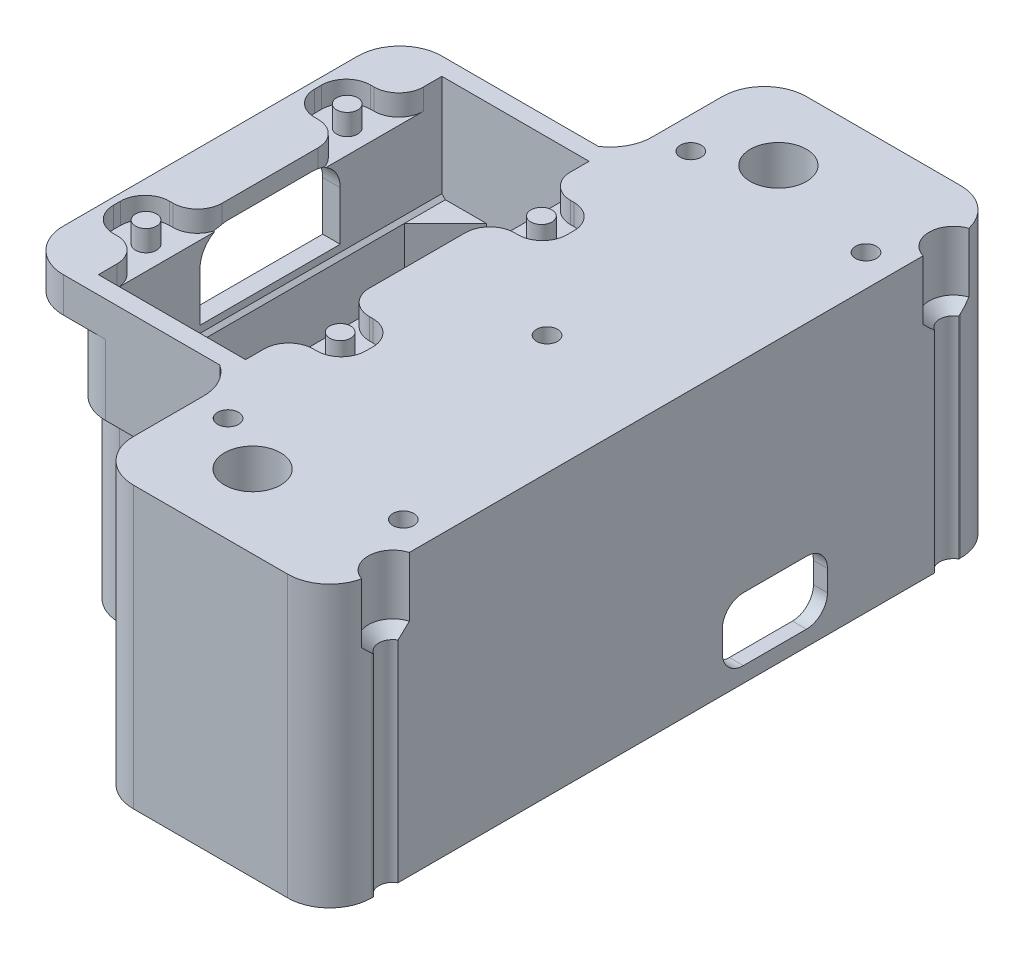
SolidWorks part; units mm, degrees
ref_plane "Płaszczyzna przednia" through (0, 0, 0) normal (0, 0, 1) x (1, 0, 0)
ref_plane "Płaszczyzna górna" through (0, 0, 0) normal (0, 1, 0) x (1, 0, 0)
ref_plane "Płaszczyzna prawa" through (0, 0, 0) normal (1, 0, 0) x (0, 0, -1)
sketch "Szkic1" plane through (0, 0, 0) normal (0, 1, 0) x (1, 0, 0)
  line L0 (0, 14.5) -> (0, -14.5) construction
  line L1 (10, 14.5) -> (10, -14.5)
  line L2 (-10, 14.5) -> (-10, -14.5)
  line L4 (-12, 26) -> (12, 26)
  line L5 (-12, 26) -> (-12, -26)
  line L6 (-12, -26) -> (12, -26)
  line L7 (12, 26) -> (12, -26)
  line L8 (-12, 26) -> (12, -26) construction
  line L9 (-12, -26) -> (12, 26) construction
  arc A0 (10, 14.5) -> (-10, 14.5) centre (0, 14.5) ccw
  arc A1 (-10, -14.5) -> (10, -14.5) centre (0, -14.5) ccw
  point P2 (0, 0)
  point P8 (0, 0)
  dimension "D2" = 10
  dimension "D1" = 29
  dimension "D3" = 24
  dimension "D4" = 52
extrude "Dodanie-wyciągnięcie1" add sketch "Szkic1" along normal blind 25
sketch "Szkic2" plane through (0, 25, 0) normal (0, 1, 0) x (1, 0, 0)
  line L1 (-10.5, 24.5) -> (10.5, 24.5)
  line L2 (-10.5, 24.5) -> (-10.5, -24.5)
  line L3 (-10.5, -24.5) -> (10.5, -24.5)
  line L4 (10.5, 24.5) -> (10.5, -24.5)
  line L5 (-10.5, 24.5) -> (10.5, -24.5) construction
  line L6 (-10.5, -24.5) -> (10.5, 24.5) construction
  line L7 (-13, 27) -> (13, 27)
  line L8 (-13, 27) -> (-13, -27)
  line L9 (-13, -27) -> (13, -27)
  line L10 (13, 27) -> (13, -27)
  line L11 (-13, 27) -> (13, -27) construction
  line L12 (-13, -27) -> (13, 27) construction
  point P0 (0, 0)
  point P7 (0, 0)
  dimension "D1" = 26
  dimension "D2" = 54
  dimension "D3" = 21
  dimension "D4" = 49
extrude "Dodanie-wyciągnięcie2" add sketch "Szkic2" along normal blind 12
sketch "Szkic3" plane through (0, 37, 0) normal (0, 1, 0) x (1, 0, 0)
  line L0 (13, -27) -> (13, 27) construction
  line L1 (-19, 27) -> (19, 27)
  line L2 (-19, 27) -> (-19, -27)
  line L3 (-19, -27) -> (19, -27)
  line L4 (19, 27) -> (19, -27)
  line L5 (-19, 27) -> (19, -27) construction
  line L6 (-19, -27) -> (19, 27) construction
  line L7 (-13, -27) -> (13, -27) construction
  line L9 (-10.5, 24.5) -> (10.5, 24.5)
  line L10 (-10.5, 24.5) -> (-10.5, -24.5)
  line L11 (-10.5, -24.5) -> (10.5, -24.5)
  line L12 (10.5, 24.5) -> (10.5, -24.5)
  line L13 (-10.5, 24.5) -> (10.5, -24.5) construction
  line L14 (-10.5, -24.5) -> (10.5, 24.5) construction
  point P0 (0, 0)
  point P10 (0, 0)
  dimension "D1" = 6
extrude "Dodanie-wyciągnięcie3" add sketch "Szkic3" against normal blind 2
sketch "Szkic4" plane through (0, 37, 0) normal (0, 1, 0) x (1, 0, 0)
  line L0 (10, 24.5) -> (-10, 24.5)
  line L1 (-19, 27) -> (19, 27)
  line L2 (-19, 27) -> (-19, -27)
  line L3 (-19, -27) -> (19, -27)
  line L4 (19, 27) -> (19, -27)
  line L5 (-19, 27) -> (19, -27) construction
  line L6 (-19, -27) -> (19, 27) construction
  line L7 (10.5, 24.5) -> (-10.5, 24.5) construction
  line L8 (-10, 24.5) -> (-10, 18.35)
  line L9 (-10, 18.35) -> (-18, 18.35)
  line L10 (-18, 18.35) -> (-18, 10.35)
  line L11 (-18, 10.35) -> (-10, 10.35)
  line L12 (-10, 10.35) -> (-10, -10.35)
  line L13 (-10, -10.35) -> (-18, -10.35)
  line L14 (-18, -10.35) -> (-18, -18.35)
  line L15 (-18, -18.35) -> (-10, -18.35)
  line L16 (10, -24.5) -> (-10, -24.5)
  line L17 (-10.5, -24.5) -> (10.5, -24.5) construction
  line L18 (-10, -24.5) -> (-10, -18.35)
  line L19 (0, -20.35) -> (0, 20.35) construction
  line L20 (10, -24.5) -> (10, -18.35)
  line L21 (18, -18.35) -> (10, -18.35)
  line L22 (18, -10.35) -> (18, -18.35)
  line L23 (10, -10.35) -> (18, -10.35)
  line L24 (10, 10.35) -> (10, -10.35)
  line L25 (18, 10.35) -> (10, 10.35)
  line L26 (18, 18.35) -> (18, 10.35)
  line L27 (10, 18.35) -> (18, 18.35)
  line L28 (10, 24.5) -> (10, 18.35)
  line L29 (19, 27) -> (19, -27)
  point P0 (0, 0)
  point P24 (-18, -14.35)
  point P25 (-18, 14.35)
  point P29 (0, -24.5)
  point P37 (0, 24.5)
  line M8 (-19, -27) -> (19, -27)
  line M9 (19, -27) -> (19, 27)
  line M10 (19, 27) -> (-19, 27)
  line M11 (-19, 27) -> (-19, -27)
  line M12 (-10.5, 24.5) -> (10.5, 24.5)
  line M13 (10.5, 24.5) -> (10.5, -24.5)
  line M14 (10.5, -24.5) -> (-10.5, -24.5)
  line M15 (-10.5, -24.5) -> (-10.5, 24.5)
  dimension "D1" = 8
  dimension "D2" = 8
  dimension "D3" = 28.7
  dimension "D4" = 8
  dimension "D5" = 1
extrude "Dodanie-wyciągnięcie4" add sketch "Szkic4" along normal blind 3 contours L27 L26 L25 L23 L22 L21 L15 L14 L13 L11 L10 L9 M11 M8 M9 M10 M13 M14 M15 M12 region at (0, 37, -26.3397)
fillet "Zaokrąglenie1" radius 3.5 16 edges at (-18, 38.5, -10.35) (-18, 38.5, -18.35) (-18, 38.5, 10.35) (-18, 38.5, 18.35) (18, 38.5, -10.35) (18, 38.5, -18.35) (18, 38.5, 10.35) (18, 38.5, 18.35) (10.5, 38.5, 10.35) (10.5, 38.5, 18.35) (10.5, 38.5, -18.35) (10.5, 38.5, -10.35) (-10.5, 38.5, -18.35) (-10.5, 38.5, -10.35) (-10.5, 38.5, 10.35) (-10.5, 38.5, 18.35)
sketch "Szkic5" plane through (0, 37, 0) normal (0, 1, 0) x (1, 0, 0)
  line L0 (18, -14.35) -> (13.85, -14.35) construction
  line L3 (18, -13.85) -> (18, -14.85) construction
  line L6 (18, 14.35) -> (13.85, 14.35) construction
  line L9 (18, 14.85) -> (18, 13.85) construction
  line L13 (0, -22) -> (0, 22) construction
  circle A0 centre (13.85, -14.35) radius 1.5
  circle A1 centre (13.85, 14.35) radius 1.5
  circle A2 centre (-13.85, -14.35) radius 1.5
  circle A3 centre (-13.85, 14.35) radius 1.5
  dimension "D1" = 3
  dimension "D2" = 3
  dimension "D3" = 4.15
  dimension "D4" = 4.15
extrude "Dodanie-wyciągnięcie9" add sketch "Szkic5" along normal blind 3
sketch "Szkic7" plane through (-19, 0, 0) normal (-1, 0, 0) x (0, 0, 1)
  line L1 (-10, 37.5) -> (10, 37.5)
  line L2 (-10, 37.5) -> (-10, 26.5)
  line L3 (-10, 26.5) -> (10, 26.5)
  line L4 (10, 37.5) -> (10, 26.5)
  line L5 (-10, 37.5) -> (10, 26.5) construction
  line L6 (-10, 26.5) -> (10, 37.5) construction
  line L7 (0, 32) -> (0, 40) construction
  line L10 (-27, 40) -> (27, 40) construction
  point P0 (0, 32)
  dimension "D1" = 20
  dimension "D2" = 11
  dimension "D3" = 8
extrude "Wytnij-wyciągnięcie2" cut sketch "Szkic7" against normal up to next
sketch "Szkic8" plane through (0, 0, 0) normal (0, 1, 0) x (1, 0, 0)
  line L1 (12, -48) -> (46, -48)
  line L2 (12, -48) -> (12, 48)
  line L3 (12, 48) -> (46, 48)
  line L4 (46, -48) -> (46, 48)
  line L5 (12, -48) -> (46, 48) construction
  line L6 (12, 48) -> (46, -48) construction
  line L8 (14, 46) -> (44, 46)
  line L9 (14, 46) -> (14, -46)
  line L10 (14, -46) -> (44, -46)
  line L11 (44, 46) -> (44, -46)
  line L12 (14, 46) -> (44, -46) construction
  line L13 (14, -46) -> (44, 46) construction
  line L14 (12, -26) -> (12, 26) construction
  line L15 (29, 0) -> (0, 0) construction
  point P0 (29, 0)
  point P12 (29, 0)
  dimension "D2" = 34
  dimension "D3" = 96
  dimension "D4" = 92
  dimension "D5" = 30
extrude "Dodanie-wyciągnięcie5" add sketch "Szkic8" along normal blind 18.5
sketch "Szkic9" plane through (0, 18.5, 0) normal (0, 1, 0) x (1, 0, 0)
  line L1 (12, -48) -> (46, -48)
  line L2 (12, -48) -> (12, 48)
  line L3 (12, 48) -> (46, 48)
  line L4 (46, -48) -> (46, 48)
  line L5 (12, -48) -> (46, 48) construction
  line L6 (12, 48) -> (46, -48) construction
  point P4 (29, 0)
extrude "Dodanie-wyciągnięcie6" add sketch "Szkic9" along normal blind 3
sketch "Szkic10" plane through (0, 21.5, 0) normal (0, 1, 0) x (1, 0, 0)
  line L0 (0, 0) -> (29, 0) construction
  line L1 (12, -26) -> (12, -48) construction
  line L4 (24.5, -37.5) -> (24.5, 37.5) construction
  circle A0 centre (24.5, 37.5) radius 1.9
  circle A1 centre (24.5, -37.5) radius 1.9
  point P13 (24.5, 0)
  dimension "D2" = 3.8
  dimension "D3" = 3.8
  dimension "D1" = 75
  dimension "D4" = 12.5
extrude "Wytnij-wyciągnięcie3" cut sketch "Szkic10" against normal through all
fillet "Zaokrąglenie2" radius 4 4 edges at (14, 9.25, -46) (44, 9.25, -46) (44, 9.25, 46) (14, 9.25, 46)
sketch "Szkic11" plane through (0, 21.5, 0) normal (0, 1, 0) x (1, 0, 0)
  line L1 (12, -48) -> (46, -48)
  line L2 (12, -48) -> (12, 48)
  line L3 (12, 48) -> (46, 48)
  line L4 (46, -48) -> (46, 48)
  line L5 (12, -48) -> (46, 48) construction
  line L6 (12, 48) -> (46, -48) construction
  circle A0 centre (24.5, 37.5) radius 4
  circle A1 centre (24.5, -37.5) radius 4
  point P10 (29, 0)
  dimension "D1" = 8
  dimension "D2" = 8
extrude "Dodanie-wyciągnięcie7" add sketch "Szkic11" along normal up to surface (3.5 mm away) up to face at (0, 25, 0)
sketch "Szkic13" plane through (0, 40, 0) normal (0, 1, 0) x (1, 0, 0)
  line L0 (29, 48) -> (29, -48) construction
  line L3 (29, 0) -> (41.5, 0) construction
  line L4 (41.5, 33) -> (41.5, -33) construction
  line L5 (12, -48) -> (46, -48) construction
  line L6 (46, 48) -> (12, 48) construction
  circle A0 centre (41.5, 33) radius 1.5
  circle A1 centre (41.5, -33) radius 1.5
  circle A2 centre (16.5, -33) radius 1.5
  circle A3 centre (16.5, 33) radius 1.5
  circle A4 centre (29, 0) radius 1.5
  point P12 (41.5, 0)
  dimension "D3" = 3
  dimension "D4" = 3
  dimension "D5" = 3
  dimension "D1" = 12.5
  dimension "D2" = 66
sketch "Szkic20" plane through (0, 25, 0) normal (0, 1, 0) x (1, 0, 0)
  line L8 (12, 27) -> (13, 27)
  line L9 (13, 27) -> (13, -27)
  line L10 (13, -27) -> (12, -27)
  line L11 (12, -27) -> (12, -48)
  line L12 (12, -48) -> (46, -48)
  line L13 (46, -48) -> (46, 48)
  line L14 (46, 48) -> (12, 48)
  line L15 (12, 48) -> (12, 27)
  line L16 (12, 27) -> (13, 27)
  line L17 (13, 27) -> (13, -27)
  line L18 (13, -27) -> (12, -27)
  line L19 (12, -27) -> (12, -48)
  line L20 (12, -48) -> (46, -48)
  line L21 (46, -48) -> (46, 48)
  line L22 (46, 48) -> (12, 48)
  line L23 (12, 48) -> (12, 27)
  circle A0 centre (24.5, 37.5) radius 4 construction
  circle A1 centre (24.5, -37.5) radius 4 construction
  circle A2 centre (24.5, 37.5) radius 4
  circle A3 centre (24.5, -37.5) radius 4
  dimension "D1" = 0
extrude "Dodanie-wyciągnięcie10" add sketch "Szkic20" along normal up to surface (10 mm away) up to face at (16, 35, 0)
sketch "Szkic21" plane through (0, 35, 0) normal (0, 1, 0) x (1, 0, 0)
  line L8 (12, 27) -> (19, 27)
  line L9 (19, 27) -> (19, -27)
  line L10 (19, -27) -> (12, -27)
  line L11 (12, -27) -> (12, -48)
  line L12 (12, -48) -> (46, -48)
  line L13 (46, -48) -> (46, 48)
  line L14 (46, 48) -> (12, 48)
  line L15 (12, 48) -> (12, 27)
  line L16 (12, 27) -> (19, 27)
  line L17 (19, 27) -> (19, -27)
  line L18 (19, -27) -> (12, -27)
  line L19 (12, -27) -> (12, -48)
  line L20 (12, -48) -> (46, -48)
  line L21 (46, -48) -> (46, 48)
  line L22 (46, 48) -> (12, 48)
  line L23 (12, 48) -> (12, 27)
  circle A0 centre (24.5, 37.5) radius 4 construction
  circle A1 centre (24.5, 37.5) radius 4
  circle A2 centre (24.5, -37.5) radius 4 construction
  circle A3 centre (24.5, -37.5) radius 4
  dimension "D1" = 0
extrude "Dodanie-wyciągnięcie11" add sketch "Szkic21" along normal up to surface (5 mm away) up to face at (0, 40, 0)
extrude "Wytnij-wyciągnięcie4" cut sketch "Szkic13" against normal blind 6
sketch "Szkic14" plane through (0, 25, 0) normal (0, 1, 0) x (1, 0, 0)
  line L0 (10, 0) -> (10, 18.6421)
  line L1 (10, -14.5) -> (10, 14.5) construction
  line L2 (-10.5, 24.5) -> (10.5, 24.5) construction
  line L3 (-4.1421, 24.5) -> (4.1421, 24.5)
  line L4 (10, 18.6421) -> (4.1421, 24.5)
  line L5 (4.1421, 24.5) -> (10, 24.5) construction
  line L6 (10, 18.6421) -> (10, 24.5) construction
  line L7 (10, 0) -> (10, -18.6421)
  line L8 (10.5, -24.5) -> (-10.5, -24.5) construction
  line L9 (4.1421, -24.5) -> (-4.1421, -24.5)
  line L10 (4.1421, -24.5) -> (10, -18.6421)
  line L11 (10, -18.6421) -> (10, -24.5) construction
  line L12 (10, -24.5) -> (4.1421, -24.5) construction
  line L13 (0, -22) -> (0, 22) construction
  line L14 (-10, 18.6421) -> (-4.1421, 24.5)
  line L15 (-10, 0) -> (-10, 18.6421)
  line L16 (-10, 0) -> (-10, -18.6421)
  line L17 (-4.1421, -24.5) -> (-10, -18.6421)
  arc A0 (10, 14.5) -> (0, 24.5) centre (0, 14.5) ccw construction
  arc A1 (0, -24.5) -> (10, -14.5) centre (0, -14.5) ccw construction
  point P25 (0, 24.5)
  point P29 (0, -24.5)
  dimension "D1" = 45
  dimension "D2" = 45
extrude "Wytnij-wyciągnięcie5" cut sketch "Szkic14" against normal through all
chamfer "Sfazowanie1" distance 0.5 angle 45 2 edges at (10.5, 25, 0) (-10.5, 25, 0)
chamfer "Sfazowanie2" distance 2.1 angle 45 2 edges at (24.5, 21.5, -33.5) (24.5, 21.5, 41.5)
fillet "Zaokrąglenie3" radius 6 12 edges at (12, 12.5, 26) (12, 12.5, -26) (-19, 37.5, 27) (-19, 37.5, -27) (-12, 12.5, -26) (-12, 12.5, 26) (12, 20, -48) (46, 20, -48) (46, 20, 48) (12, 20, 48) (-13, 30, -27) (-13, 30, 27)
fillet "Zaokrąglenie4" radius 4 2 edges at (-15.7372, 37.5, 10) (-15.7372, 37.5, -10)
sketch "Szkic18" plane through (0, 40, 0) normal (0, 1, 0) x (1, 0, 0)
  line L0 (46, 0) -> (47, 0) construction
  line L2 (47, 0) -> (47, 40) construction
  line L3 (46, -42) -> (46, 42) construction
  circle A0 centre (47, 40) radius 3.5
  circle A1 centre (47, -40) radius 3.5
  dimension "D1" = 7
  dimension "D2" = 1
  dimension "D3" = 40
extrude "Wytnij-wyciągnięcie8" cut sketch "Szkic18" against normal blind 10
chamfer "Sfazowanie3" distance 1.5 angle 45 2 edges at (43.5008, 30, -39.9242) (43.5008, 30, 39.9242)
sketch "Szkic19" plane through (0, 30, 0) normal (0, 1, 0) x (1, 0, 0)
  circle A0 centre (47, -40) radius 2
  circle A1 centre (47, 40) radius 2
  arc A2 (46, 41.7321) -> (46, 38.2679) centre (47, 40) ccw construction
extrude "Wytnij-wyciągnięcie9" cut sketch "Szkic19" against normal through all
sketch "Szkic22" plane through (46, 0, 0) normal (1, 0, 0) x (0, 0, -1)
  line L0 (-38.2679, 0) -> (38.2679, 0) construction
  line L1 (8, 2.2) -> (23, 2.2)
  line L2 (8, 2.2) -> (8, 11.2)
  line L3 (8, 11.2) -> (23, 11.2)
  line L4 (23, 2.2) -> (23, 11.2)
  line L5 (8, 2.2) -> (23, 11.2) construction
  line L6 (8, 11.2) -> (23, 2.2) construction
  line L7 (48, 40) -> (48, 0) construction
  point P4 (15.5, 6.7)
  dimension "D1" = 2.2
  dimension "D2" = 25
  dimension "D3" = 15
  dimension "D4" = 9
extrude "Wytnij-wyciągnięcie10" cut sketch "Szkic22" against normal up to next
fillet "Zaokrąglenie5" radius 3 4 edges at (45, 2.2, -23) (45, 11.2, -23) (45, 11.2, -8) (45, 2.2, -8)
